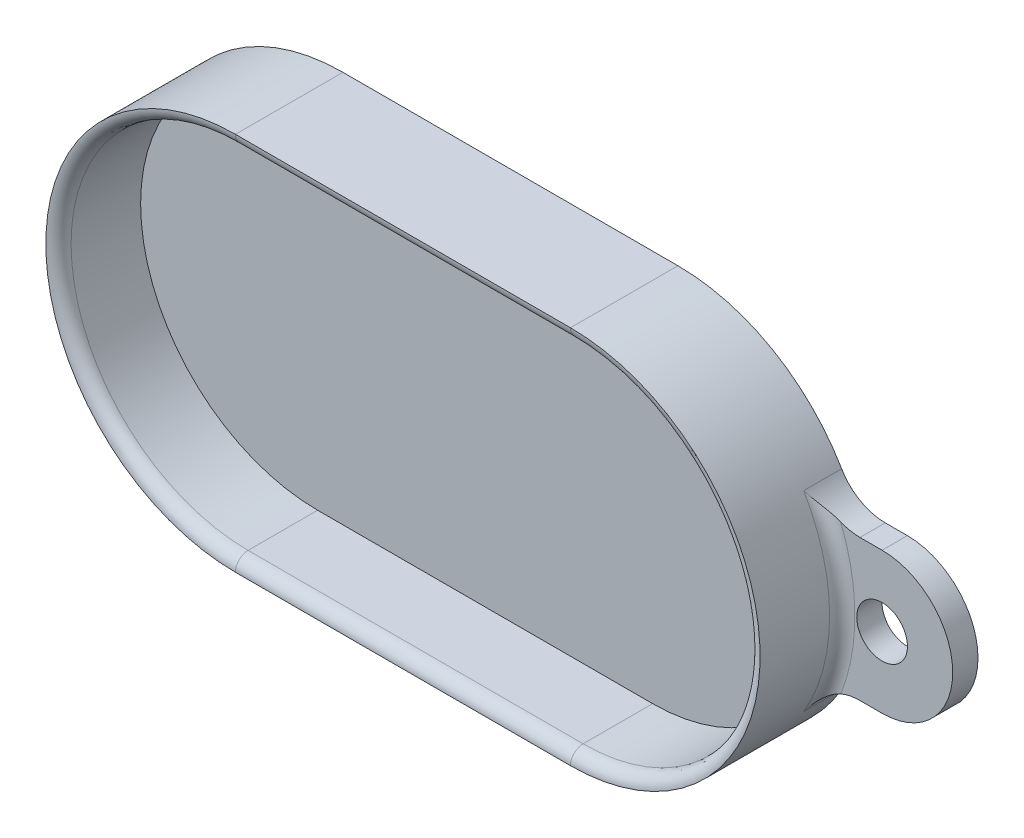
SolidWorks part; units mm, degrees
ref_plane "Front Plane" through (0, 0, 0) normal (0, 0, 1) x (1, 0, 0)
ref_plane "Top Plane" through (0, 0, 0) normal (0, 1, 0) x (1, 0, 0)
ref_plane "Right Plane" through (0, 0, 0) normal (1, 0, 0) x (0, 0, -1)
sketch "Sketch1" plane through (0, 0, 0) normal (0, 0, 1) x (1, 0, 0)
  line L0 (-10.8682, 0) -> (15.6318, 0) construction
  line L1 (-10.8682, 14) -> (15.6318, 14)
  line L2 (-10.8682, -14) -> (15.6318, -14)
  line L3 (-10.8682, -15) -> (15.6318, -15)
  line L4 (-10.8682, 15) -> (15.6318, 15)
  arc A0 (-10.8682, 14) -> (-10.8682, -14) centre (-10.8682, 0) ccw
  arc A1 (15.6318, -14) -> (15.6318, 14) centre (15.6318, 0) ccw
  arc A2 (-10.8682, 15) -> (-10.8682, -15) centre (-10.8682, 0) ccw
  arc A3 (15.6318, -15) -> (15.6318, 15) centre (15.6318, 0) ccw
  point P13 (-24.8682, 0)
  point P14 (29.6318, 0)
  dimension "D2" = 28
  dimension "D1" = 26.5
  dimension "D4" = 54.5
  dimension "D3" = 1
extrude "Boss-Extrude1" add sketch "Sketch1" along normal blind 6.5
sketch "Sketch2" plane through (0, 0, 0) normal (0, 0, -1) x (-1, 0, 0)
  line L0 (10.8682, -15) -> (-15.6318, -15)
  line L1 (-15.6318, 15) -> (10.8682, 15)
  line L2 (-33.7817, -5.5864) -> (-32.036, -5.5864)
  line L3 (-33.7817, 5.5864) -> (-32.036, 5.5864)
  arc A0 (10.8682, -15) -> (10.8682, 15) centre (10.8682, 0) ccw
  arc A1 (-15.6318, 15) -> (-28.5825, 7.5682) centre (-15.6318, 0) ccw
  circle A2 centre (-33.7817, 0) radius 2.0059
  arc A3 (-33.7817, 5.5864) -> (-33.7817, -5.5864) centre (-33.7817, 0) ccw
  arc A4 (-28.5825, -7.5682) -> (-15.6318, -15) centre (-15.6318, 0) ccw
  arc A5 (-28.5825, 7.5682) -> (-32.036, 5.5864) centre (-32.036, 9.5864) cw
  arc A6 (-28.5825, -7.5682) -> (-32.036, -5.5864) centre (-32.036, -9.5864) ccw
  point P20 (-29.5527, -5.5864)
  dimension "D1" = 4
extrude "Boss-Extrude2" add sketch "Sketch2" along normal blind 2
fillet "Fillet1" radius 1 1 edges at (30.6318, 0, 0)
fillet "Fillet2" radius 1 4 edges at (29.6318, 0, 6.5) (2.3818, -14, 6.5) (-24.8682, 0, 6.5) (2.3818, 14, 6.5)
